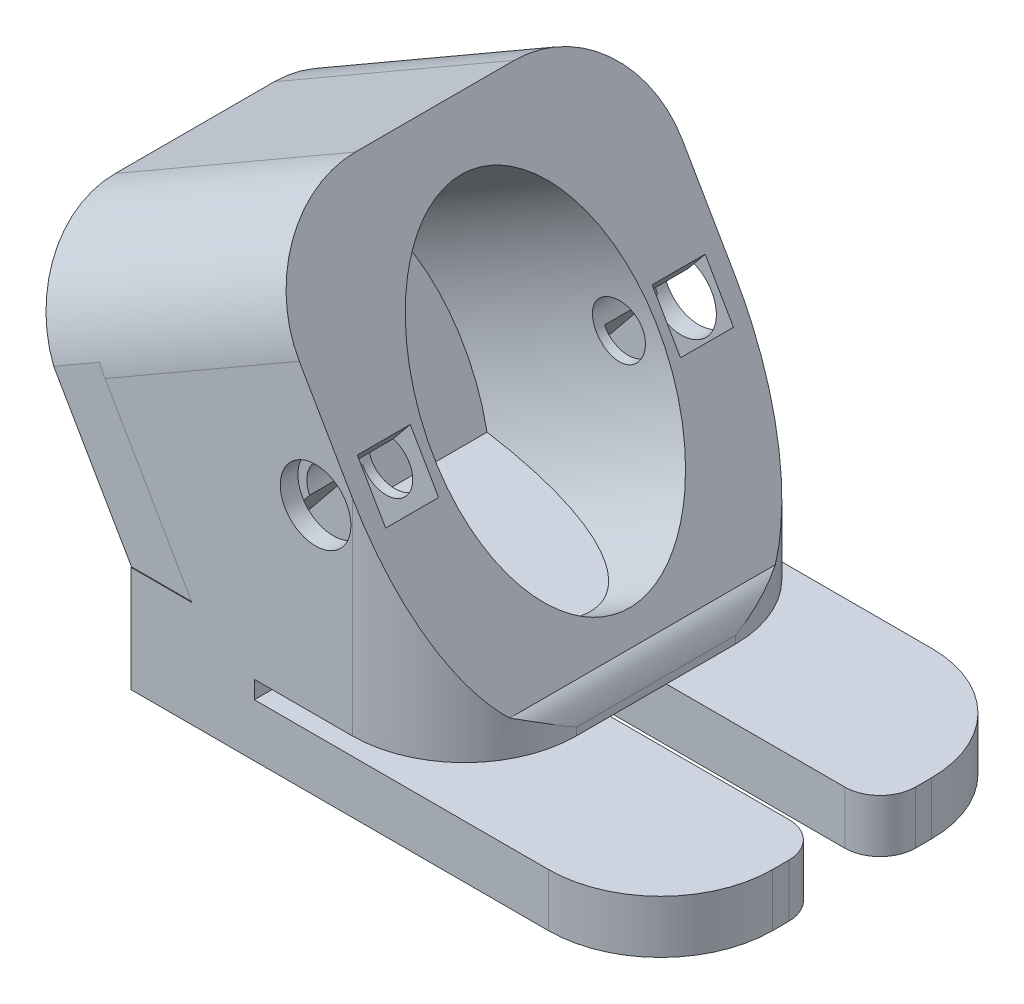
SolidWorks part; units mm, degrees
note: The reader was unsure of these and kept them because the rebuilt part matched: shared geometry of "Sketch7<3>".
ref_plane "Front Plane" through (0, 0, 0) normal (0, 0, 1) x (1, 0, 0)
ref_plane "Top Plane" through (0, 0, 0) normal (0, 1, 0) x (1, 0, 0)
ref_plane "Right Plane" through (0, 0, 0) normal (1, 0, 0) x (0, 0, -1)
sketch "Sketch1" plane through (0, 0, 0) normal (0, 0, 1) x (1, 0, 0)
  line L0 (0, 0) -> (16.4978, 9.525)
  line L1 (0, 0) -> (20.7767, 0) construction
  line L2 (12.7, 0) -> (19.6728, 4.0257)
  line L3 (19.6928, 3.9911) -> (16.4978, 9.525) construction
  point P9 (14.1735, 0.8507)
  dimension "D1" = 19.05
  dimension "D2" = 30
  dimension "D3" = 6.35
  dimension "D4" = 8.0515
  dimension "D5" = 6.35
ref_plane "Plane1" through (16.4978, 9.525, 0) normal (0.866, 0.5, 0) x (0, 0, -1)
sketch "Sketch2" plane through (16.4978, 9.525, 0) normal (0.866, 0.5, 0) x (0, 0, -1)
  line L0 (0, 100000) -> (0, -100010.3884) construction
  line L1 (10.85, 12.525) -> (10.85, -12.525)
  line L2 (10.85, 12.525) -> (-10.85, 12.525)
  line L3 (10.85, -12.525) -> (-10.85, -12.525)
  line L4 (-10.85, 12.525) -> (-10.85, -12.525)
  line L5 (10.85, 12.525) -> (-10.85, -12.525) construction
  line L6 (10.85, -12.525) -> (-10.85, 12.525) construction
  ellipse E0 centre (0, 0) end of major axis (0, 9.525) minor radius 6.35
  point P1 (-10.85, 0)
  point P7 (0, -12.525)
  dimension "D1" = 19.05
  dimension "D2" = 12.7
  dimension "D3" = 4.5
  dimension "D4" = 3
extrude "Boss-Extrude1" add sketch "Sketch2" against normal blind 12.7
sketch "Sketch3" plane through (5.4993, 3.175, 0) normal (-0.866, -0.5, 0) x (0, 0, 1)
  line L0 (-10.85, 12.525) -> (-10.85, -12.525)
  line L1 (-10.85, 12.525) -> (10.8107, 12.525)
  line L2 (-10.85, -12.525) -> (10.8107, -12.525)
  line L3 (10.8107, 12.525) -> (10.8107, -12.525)
extrude "Boss-Extrude2" add sketch "Sketch3" along normal blind 3
sketch "Sketch5" plane through (0, 0, 0) normal (0, 1, 0) x (-1, 0, 0)
  line L0 (-22.7603, 10.85) -> (-22.7603, -10.85)
  line L1 (-22.7603, 10.85) -> (-3.8682, 10.85)
  line L2 (-22.7603, -10.85) -> (-3.8682, -10.85)
  line L3 (-3.8682, 10.85) -> (-3.8682, -10.85)
  line L8 (-22.7603, 10.85) -> (-22.7603, -10.85) construction
extrude "Boss-Extrude3" add sketch "Sketch5" against normal blind 2
sketch "Sketch6" plane through (0, -2, 0) normal (0, -1, 0) x (1, 0, 0)
  line L0 (3.8682, -10.85) -> (3.8682, 10.85)
  line L1 (3.8682, -10.85) -> (33.8682, -10.85)
  line L2 (3.8682, 10.85) -> (33.8682, 10.85)
  line L3 (33.8682, -10.85) -> (33.8682, 10.85)
  line L10 (3.8682, 10.85) -> (8.487, 10.85) construction
  line L11 (3.8682, -10.85) -> (3.8682, 10.85) construction
  dimension "D1" = 30
extrude "Boss-Extrude4" add sketch "Sketch6" along normal blind 4
sketch "Sketch7" plane through (33.8682, 0, 0) normal (1, 0, 0) x (0, 0, -1)
  line L0 (-10.85, -2) -> (10.85, -2)
  line L1 (-10.85, -2) -> (-10.85, -3)
  line L2 (10.85, -2) -> (10.85, -3)
  line L3 (-10.85, -3) -> (10.85, -3)
  line L4 (-1.5875, -3) -> (1.5875, -3)
  line L5 (-10.85, -6) -> (-10.85, -2) construction
  line L6 (-10.85, -6) -> (10.85, -6)
  line L7 (-10.85, -6) -> (-10.85, -13.2725)
  line L8 (10.85, -6) -> (10.85, -13.2725)
  line L9 (-10.85, -13.2725) -> (10.85, -13.2725)
  line L10 (-1.5875, -3) -> (-1.5875, -6)
  line L11 (1.5875, -3) -> (1.5875, -6)
  line L12 (-1.5875, -6) -> (1.5875, -6)
  point P0 (0, -3)
  point P11 (0, -3)
  line M4 (-10.85, -6) -> (10.85, -6)
  dimension "D1" = 1
  dimension "D2" = 3.175
extrude "Cut-Extrude2" cut sketch "Sketch7" against normal blind 23 contours L2 L3 L1 L0 | L10 L12 L11 L4
extrude "Cut-Extrude3" cut sketch "Sketch7<3>" against normal through all contours L7 L9 L8 M4
sketch "Sketch7<3>" plane through (33.8682, 0, 0) normal (1, 0, 0) x (0, 0, -1) same geometry as "Sketch7"
ref_plane "Plane2" through (3.175, -5.4993, 0) normal (0.5, -0.866, 0) x (0.866, 0.5, 0)
sketch "Sketch8" plane through (3.175, -5.4993, 6.35) normal (0.5, -0.866, 0) x (0.75, 0.433, -0.5)
  line L0 (13.7985, 1.5003) -> (14.5485, 0.2012)
  line L1 (13.7985, 1.5003) -> (-3.522, -8.4997)
  line L2 (14.5485, 0.2012) -> (-2.772, -9.7988)
  line L3 (-3.522, -8.4997) -> (-2.772, -9.7988)
  line L4 (12.7, 0) -> (19.6728, 4.0257) construction
  dimension "D1" = 1.5
  dimension "D2" = 20
ref_plane "Plane3" through (19.6728, 0, 0) normal (1, 0, 0) x (0, 0, -1)
sketch "Sketch11" plane through (19.6728, 0.1949, 0) normal (-1, 0, 0) x (0, 0, -1)
  circle A0 centre (0, -3.8309) radius 1
  dimension "D1" = 2
extrude "Cut-Extrude8" cut sketch "Sketch11" along normal through all
sketch "Sketch13" plane through (0, 0, 0) normal (0, 0, 1) x (1, 0, 0)
  line L0 (16.4978, 9.525) -> (3.8682, -6)
  point P3 (0, 0)
  point P4 (0, 0)
ref_plane "Plane4" through (16.4978, 9.525, 0) normal (0.6311, 0.7757, 0) x (0.7757, -0.6311, 0)
sketch "Sketch15" plane through (16.4978, 9.525, 0) normal (0.6311, 0.7757, 0) x (0.7757, -0.6311, 0)
  line L0 (-11.7031, -10.85) -> (10.2768, -10.85) construction
  line L1 (-1.5, -6.85) -> (1.5, -6.85)
  line L2 (-1.5, -6.85) -> (-1.5, -9.85)
  line L3 (-1.5, -9.85) -> (1.5, -9.85)
  line L4 (1.5, -6.85) -> (1.5, -9.85)
  line L6 (0, 0) -> (0, -5.6108) construction
  point P8 (0, -9.85)
  dimension "D1" = 3
  dimension "D2" = 3
  dimension "D3" = 1
extrude "Cut-Extrude9" cut sketch "Sketch15" against normal through all both and the other way through all
sketch "Sketch9" plane through (0, 0, -10.85) normal (0, 0, -1) x (-1, 0, 0)
  line L0 (0, 0) -> (-16.4978, 9.525) construction
  line L1 (-10.2353, 20.372) -> (-21.997, 0) construction
  circle A0 centre (-14.3327, 8.275) radius 1.5
  dimension "D1" = 3
  dimension "D2" = 2.5
extrude "Cut-Extrude4" cut sketch "Sketch9" against normal up to next contours A0
sketch "Sketch10" plane through (0, 0, -10.85) normal (0, 0, -1) x (-1, 0, 0)
  circle A0 centre (-14.3327, 8.275) radius 2
  dimension "D1" = 4
extrude "Cut-Extrude7" cut sketch "Sketch10" against normal blind 1
mirror "Mirror1" about plane through (0, 0, 0) normal (0, 0, 1) of "Cut-Extrude9", "Cut-Extrude4", "Cut-Extrude7"
fillet "Fillet5" radius 6.35 6 edges at (33.8682, -4.5, 10.85) (33.8682, -4.5, -10.85) (22.7603, -1, -10.85) (22.7603, -1, 10.85) (4.736, 17.197, 10.85) (3.437, 16.447, -10.85)
fillet "Fillet6" radius 2 2 edges at (33.8682, -4.5, -1.5875) (33.8682, -4.5, 1.5875)
fillet "Fillet7" radius 2 1 edges at (22.7603, 0, 0)
